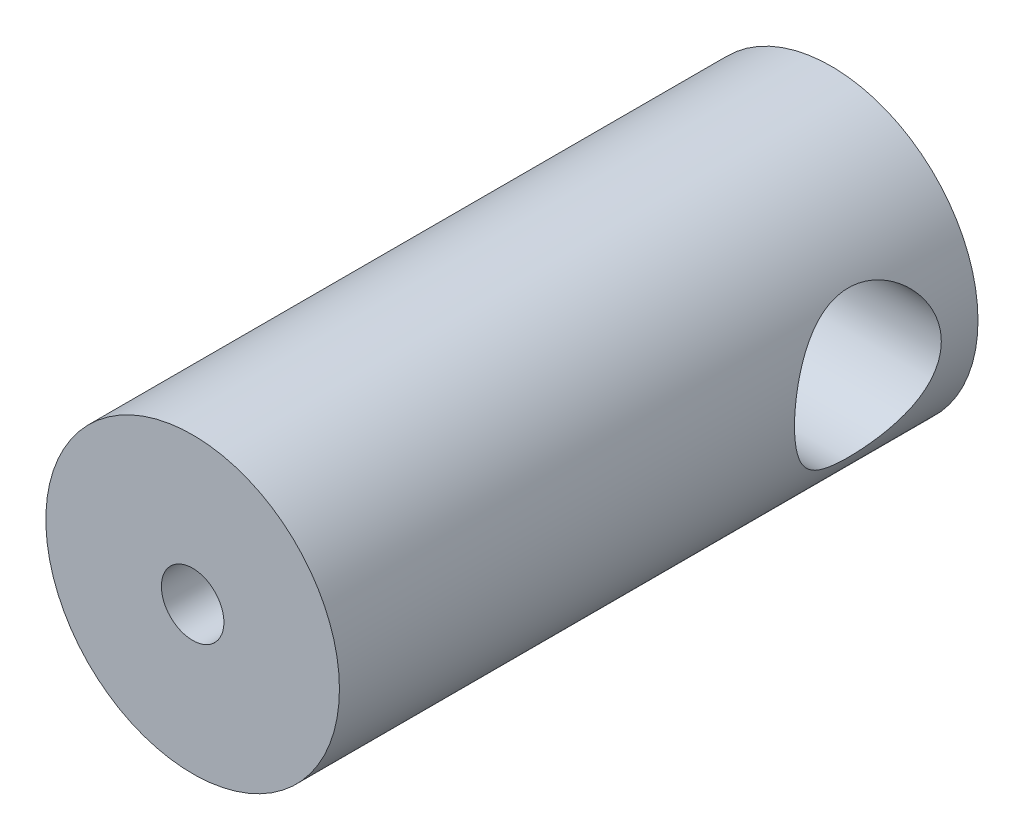
SolidWorks part; units mm, degrees
ref_plane "Front Plane" through (0, 0, 0) normal (0, 0, 1) x (1, 0, 0)
ref_plane "Top Plane" through (0, 0, 0) normal (0, 1, 0) x (1, 0, 0)
ref_plane "Right Plane" through (0, 0, 0) normal (1, 0, 0) x (0, 0, -1)
sketch "Sketch1" plane through (0, 0, 0) normal (0, 0, 1) x (1, 0, 0)
  circle A0 centre (0, 0) radius 6.35
  dimension "D1" = 12.7
extrude "Boss-Extrude1" add sketch "Sketch1" along normal blind 27.6225
sketch "Sketch2" plane through (0, 0, 27.6225) normal (0, 0, 1) x (1, 0, 0)
  circle A0 centre (0, 0) radius 1.905
  dimension "D1" = 3.81
extrude "Cut-Extrude1" [suppressed] cut sketch "Sketch2" against normal blind 12.7
sketch "Sketch3" plane through (0, 0, 0) normal (1, 0, 0) x (0, 0, -1)
  line L0 (-27.6225, 6.35) -> (-27.6225, -6.35) construction
  circle A0 centre (-4.7625, 0) radius 3.175
  dimension "D2" = 6.35
  dimension "D1" = 22.86
extrude "Cut-Extrude2" cut sketch "Sketch3" against normal through all and the other way through all
hole_wizard "#6-32 Tapped Hole1" positions "Sketch5" profile "Sketch6" tap size "#6-32" standard "ANSI Inch"
sketch "Sketch5" plane through (0, 0, 27.6225) normal (0, 0, 1) x (1, 0, 0)
  point P0 (0, 0)
sketch "Sketch6" plane through (0, 0, 27.6225) normal (1, 0, 0) x (0, -1, 0)
  line L0 (0, 0) -> (0, 13.5127)
  line L1 (0, 13.5127) -> (1.3525, 12.7)
  line L2 (1.3525, 12.7) -> (1.3525, 0)
  line L5 (1.3525, 0) -> (0, 0)
  line L10 (0, 13.5127) -> (-1.3526, 12.7) construction
  line L11 (0, -6.35) -> (0, 107.95) construction
  dimension "Tap Drill Dia." = 2.7051
  dimension "Tap Drill Depth" = 12.7
  dimension "Drill Angle" = 118
cosmetic thread "Hole Thread1" parameters "D1"=1.0644, "D2"=3.5052
